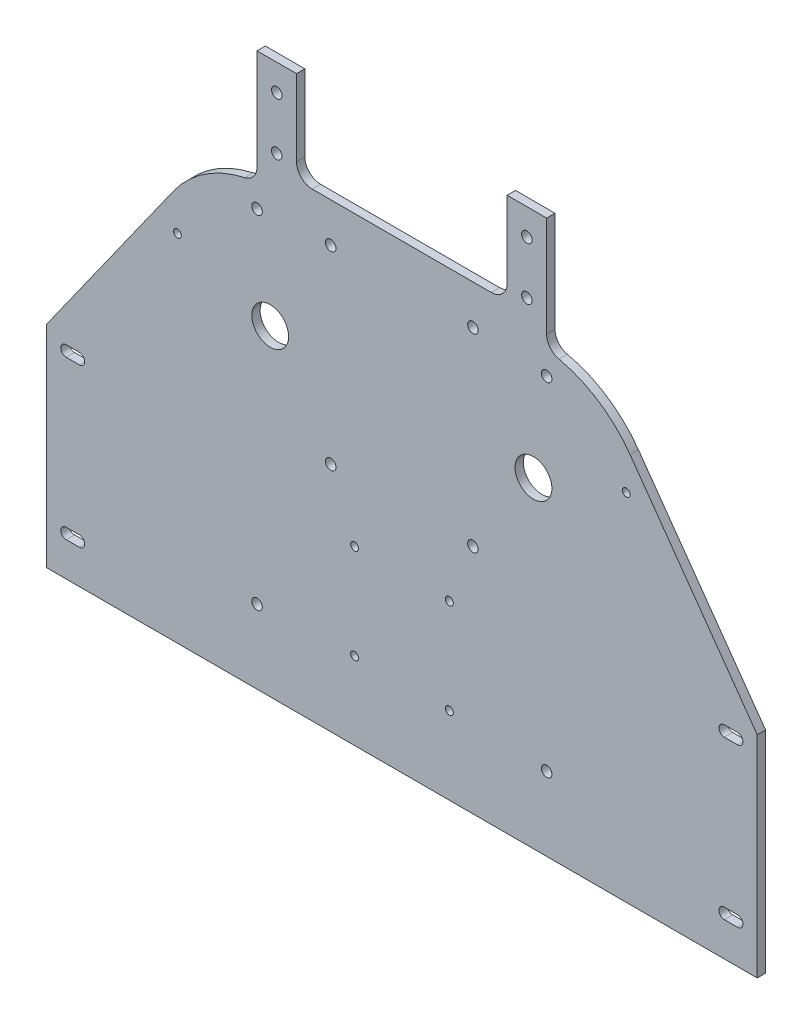
SolidWorks part; units mm, degrees
ref_plane "Front Plane" through (0, 0, 0) normal (0, 0, 1) x (1, 0, 0)
ref_plane "Top Plane" through (0, 0, 0) normal (0, 1, 0) x (1, 0, 0)
ref_plane "Right Plane" through (0, 0, 0) normal (1, 0, 0) x (0, 0, -1)
sketch "Sketch1" plane through (0, 0, 0) normal (0, 0, 1) x (1, 0, 0)
  line L1 (-100, -75) -> (100, -75)
  line L2 (-100, -75) -> (-100, 75)
  line L3 (-100, 75) -> (100, 75)
  line L4 (100, -75) -> (100, 75)
  line L5 (-100, -75) -> (100, 75) construction
  line L6 (-100, 75) -> (100, -75) construction
  line L8 (-47.5, 40) -> (47.5, 40) construction
  line L9 (0, 75) -> (0, -75) construction
  line L10 (-27, -52) -> (27, -52) construction
  line L11 (-27, -52) -> (-27, 20) construction
  line L12 (-27, 20) -> (27, 20) construction
  line L13 (27, -52) -> (27, 20) construction
  line L14 (-27, -52) -> (27, 20) construction
  line L15 (-27, 20) -> (27, -52) construction
  line L23 (-55, 70) -> (55, 70)
  line L24 (-55, 70) -> (-55, -70)
  line L25 (-55, -70) -> (55, -70)
  line L26 (55, 70) -> (55, -70)
  line L27 (-55, 70) -> (55, -70) construction
  line L28 (-55, -70) -> (55, 70) construction
  line L29 (-40, 70) -> (40, 70)
  line L30 (-40, 70) -> (-40, 35)
  line L31 (-40, 35) -> (40, 35)
  line L32 (40, 70) -> (40, 35)
  line L33 (-40, 70) -> (40, 35) construction
  line L34 (-40, 35) -> (40, 70) construction
  circle A2 centre (-47.5, 40) radius 2
  circle A3 centre (47.5, 40) radius 2
  circle A4 centre (-27, 20) radius 2
  circle A5 centre (27, 20) radius 2
  circle A6 centre (27, -52) radius 2
  circle A7 centre (-27, -52) radius 2
  circle A8 centre (-47.5, 60) radius 2
  circle A9 centre (47.5, 60) radius 2
  point P0 (0, 0)
  point P15 (0, 40)
  point P18 (0, -16)
  point P56 (0, 0)
  point P63 (0, 52.5)
  dimension "D3" = 4
  dimension "D4" = 20
  dimension "D5" = 4
  dimension "D8" = 4
  dimension "D1" = 150
  dimension "D2" = 200
  dimension "D6" = 72
  dimension "D7" = 54
  dimension "D14" = 30
  dimension "D15" = 140
  dimension "D16" = 110
  dimension "D17" = 95
  dimension "D18" = 20
  dimension "D19" = 35
  dimension "D20" = 80
extrude "Boss-Extrude1" add sketch "Sketch1" along normal blind 3.175 contours L23 L32 L31 L30 L24 L25 L26 A7 A6 A5 A4 A3 A2 region at (0, -11.8972, 0)
sketch "Sketch3" plane through (0, 0, 3.175) normal (0, 0, 1) x (1, 0, 0)
  line L0 (0, 0) -> (0, 95.843) construction
  line L1 (-50, -18) -> (-85.2385, -5.1742) construction
  line L2 (-50, -18) -> (-56.5118, 18.9303) construction
  line L3 (-50, -18) -> (-87.5, -18) construction
  circle A0 centre (-50, -18) radius 30 construction
  circle A1 centre (-50, -18) radius 45
  circle A2 centre (-50, -18) radius 37.5 construction
  circle A3 centre (-85.2385, -5.1742) radius 1.4732
  circle A5 centre (-47.5, 40) radius 2 construction
  circle A7 centre (85.2385, -5.1742) radius 1.4732
  circle A8 centre (50, -18) radius 45
  line M5 (-55, -70) -> (55, -70)
  line M11 (55, -70) -> (55, 70)
  line M13 (40, 70) -> (40, 35)
  line M14 (40, 35) -> (-40, 35)
  line M15 (-40, 35) -> (-40, 70)
  line M17 (-55, 70) -> (-55, -70)
  circle M23 centre (-47.5, 40) radius 2
  circle M24 centre (47.5, 40) radius 2
  circle M25 centre (-27, 20) radius 2
  circle M26 centre (27, 20) radius 2
  circle M27 centre (27, -52) radius 2
  circle M28 centre (-27, -52) radius 2
  dimension "D1" = 60
  dimension "D3" = 7.5
  dimension "D4" = 58
  dimension "D5" = 20
  dimension "D6" = 80
  dimension "D7" = 100
  dimension "D2" = 15
extrude "Boss-Extrude3" add sketch "Sketch3" against normal up to surface (3.175 mm away) contours A1 A3 M17 | A1 M15 M17 M5 M14 M28 M25 M23 | A8 M11 M13 M14 M5 M27 M26 M24 | A8 A7 M11 region at (-33.6109, -17.9702, 3.175) region at (33.6109, -17.9702, 3.175) region at (71.7941, -18.0321, 3.175) region at (-71.7941, -18.0321, 3.175) up to face at (0, 26.25, 0)
sketch "Sketch4" plane through (0, 0, 3.175) normal (0, 0, 1) x (1, 0, 0)
  line L1 (-60, -130) -> (-111.1989, -130)
  line L2 (-60, -130) -> (-60, -60)
  line L3 (-60, -60) -> (-110.4731, -60)
  line L4 (-135, -130) -> (-135, -60)
  line L5 (-60, -130) -> (-135, -60) construction
  line L6 (-60, -60) -> (-135, -130) construction
  line L10 (-111.1989, -130) -> (-135, -130)
  line L11 (-135, -60) -> (-86.6945, 8.0483)
  line L12 (-110.4731, -60) -> (-92.0445, -34.0394)
  line L13 (-110.4731, -60) -> (-135, -60) construction
  line L14 (-135, -95) -> (-60, -95) construction
  line L15 (-125, -60) -> (-125, -95) construction
  line L18 (-60, -130) -> (-60, -122.95)
  line L22 (-60, -60) -> (0, -60)
  line L23 (-122.5, -65) -> (-127.5, -65) construction
  line L24 (-122.5, -67.05) -> (-127.5, -67.05)
  line L25 (-122.5, -62.95) -> (-127.5, -62.95)
  line L26 (-122.5, -125) -> (-127.5, -125) construction
  line L27 (-122.5, -122.95) -> (-127.5, -122.95)
  line L28 (-122.5, -127.05) -> (-127.5, -127.05)
  line L29 (-60, -60) -> (-60, -130)
  line L30 (-60, -130) -> (0, -130)
  line L31 (0, -60) -> (0, -130)
  line L32 (-60, -60) -> (0, -130) construction
  line L33 (-60, -130) -> (0, -60) construction
  line L34 (0, -130) -> (-135, -130)
  line L35 (0, -130) -> (0, -140)
  line L36 (0, -140) -> (-135, -140)
  line L37 (-135, -130) -> (-135, -140)
  line L38 (0, -130) -> (-135, -140) construction
  line L39 (0, -140) -> (-135, -130) construction
  arc A2 (-55, 26.7214) -> (-55, -62.7214) centre (-50, -18) ccw construction
  arc A3 (-92.0445, -34.0394) -> (-86.6945, 8.0483) centre (-50, -18) cw
  circle A4 centre (-125, -65) radius 2.05 construction
  circle A6 centre (-125, -125) radius 2.05 construction
  arc A7 (-122.5, -67.05) -> (-122.5, -62.95) centre (-122.5, -65) ccw
  arc A8 (-127.5, -62.95) -> (-127.5, -67.05) centre (-127.5, -65) ccw
  arc A9 (-122.5, -122.95) -> (-122.5, -127.05) centre (-122.5, -125) cw
  arc A10 (-127.5, -127.05) -> (-127.5, -122.95) centre (-127.5, -125) cw
  point P0 (-97.5, -95)
  point P15 (-67.5, -135)
  point P31 (-30, -95)
  point P36 (-87.5, -107.6256)
  point P38 (-125, -65)
  point P48 (-125, -125)
  dimension "D7" = 4.1
  dimension "D9" = 2.05
  dimension "D1" = 60
  dimension "D2" = 60
  dimension "D3" = 75
  dimension "D4" = 70
  dimension "D5" = 10
  dimension "D6" = 20
  dimension "D8" = 10
  dimension "D10" = 5
  dimension "D11" = 5
extrude "Boss-Extrude4" add sketch "Sketch4" against normal up to surface (3.175 mm away) up to face at (-25, 20, 0)
mirror "Mirror2" about plane through (0, 0, 0) normal (1, 0, 0) of "Boss-Extrude4"
fillet "Fillet1" radius 6 4 edges at (-55, 26.7214, 1.5875) (-40, 35, 1.5875) (40, 35, 1.5875) (55, 26.7214, 1.5875)
sketch "Sketch5" plane through (0, 0, 3.175) normal (0, 0, 1) x (1, 0, 0)
  circle A0 centre (-50, -18) radius 7
  circle A1 centre (50, -18) radius 7
  circle A5 centre (-50, -18) radius 45
  circle A6 centre (-50, -18) radius 45 construction
  circle A7 centre (50, -18) radius 45
  circle A8 centre (50, -18) radius 45 construction
  dimension "D1" = 14
  dimension "D3" = 0
  dimension "D4" = 0
extrude "Cut-Extrude1" cut sketch "Sketch5" against normal blind 10
sketch "Sketch6" plane through (0, 0, 3.175) normal (0, 0, 1) x (1, 0, 0)
  line L1 (-30, -72) -> (30, -72) construction
  line L2 (-30, -72) -> (-30, -113) construction
  line L3 (-30, -113) -> (30, -113) construction
  line L4 (30, -72) -> (30, -113) construction
  line L5 (-30, -72) -> (30, -113) construction
  line L6 (-30, -113) -> (30, -72) construction
  line L7 (-17.94, -74.5) -> (18.06, -74.5) construction
  line L8 (-17.94, -74.5) -> (-17.94, -110.5) construction
  line L9 (-17.94, -110.5) -> (18.06, -110.5) construction
  line L10 (18.06, -74.5) -> (18.06, -110.5) construction
  line L11 (-17.94, -74.5) -> (18.06, -110.5) construction
  line L12 (-17.94, -110.5) -> (18.06, -74.5) construction
  circle A0 centre (-17.94, -110.5) radius 1.5
  circle A1 centre (-17.94, -74.5) radius 1.5
  circle A2 centre (18.06, -74.5) radius 1.5
  circle A3 centre (18.06, -110.5) radius 1.5
  circle A4 centre (-27, -52) radius 2 construction
  point P4 (0, -92.5)
  point P9 (0.06, -92.5)
  point P14 (-0.3375, -92.8577)
  point P15 (0, 0)
  point P19 (0.06, -91.9972)
  dimension "D3" = 3
  dimension "D1" = 41
  dimension "D2" = 60
  dimension "D4" = 36
  dimension "D5" = 36
  dimension "D6" = 12.06
  dimension "D7" = 2.5
  dimension "D8" = 20
extrude "Cut-Extrude2" cut sketch "Sketch6" against normal blind 10
sketch "Sketch7" plane through (0, 0, 3.175) normal (0, 0, 1) x (1, 0, 0)
  line L1 (-55, 18) -> (55, 18) construction
  line L2 (-55, 18) -> (-55, -112) construction
  line L3 (-55, -112) -> (55, -112) construction
  line L4 (55, 18) -> (55, -112) construction
  line L5 (-55, 18) -> (55, -112) construction
  line L6 (-55, -112) -> (55, 18) construction
  circle A0 centre (-55, 18) radius 2
  circle A1 centre (55, 18) radius 2
  circle A2 centre (55, -112) radius 2
  circle A3 centre (-55, -112) radius 2
  circle A5 centre (-17.94, -74.5) radius 1.5 construction
  point P4 (0, -47)
  point P9 (0, -69.2521)
  point P11 (0, -48.5943)
  point P12 (0, -36.6428)
  dimension "D1" = 4
  dimension "D3" = 37.5
  dimension "D2" = 130
  dimension "D4" = 110
extrude "Cut-Extrude3" cut sketch "Sketch7" against normal blind 10
